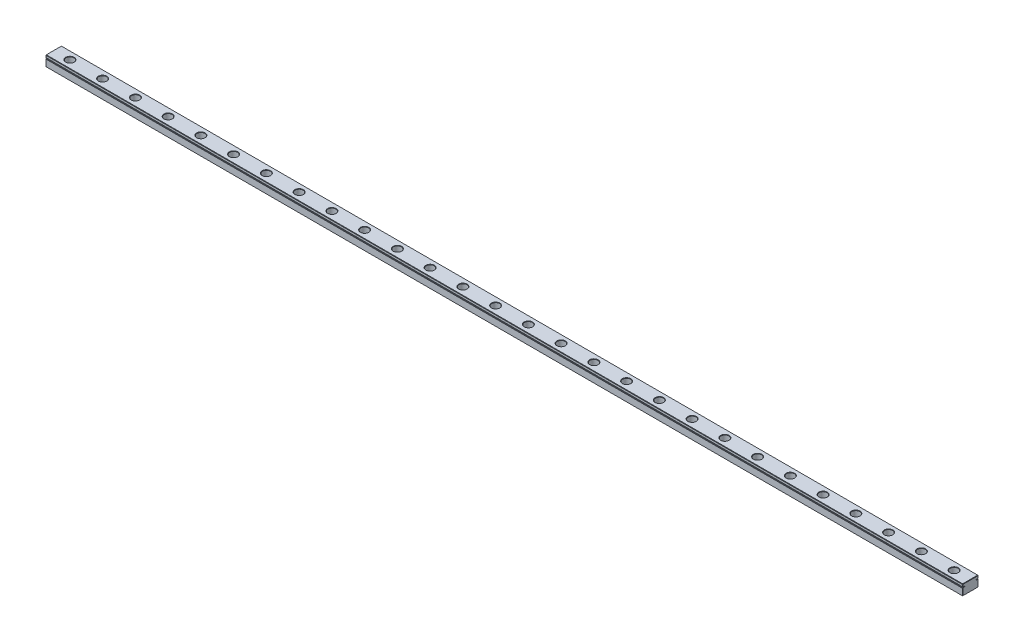
SolidWorks part; units mm, degrees
note: The reader was unsure of these and kept them because the rebuilt part matched: shared geometry of "Sketch5<3>".
ref_plane "Front Plane" through (0, 0, 0) normal (0, 0, 1) x (1, 0, 0)
ref_plane "Top Plane" through (0, 0, 0) normal (0, 1, 0) x (1, 0, 0)
ref_plane "Right Plane" through (0, 0, 0) normal (1, 0, 0) x (0, 0, -1)
sketch "Sketch1" plane through (0, 0, 0) normal (1, 0, 0) x (0, 0, -1)
  line L1 (6, -4) -> (-6, -4)
  line L2 (6, -4) -> (6, 4)
  line L3 (6, 4) -> (-6, 4)
  line L4 (-6, -4) -> (-6, 4)
  line L5 (6, -4) -> (-6, 4) construction
  line L6 (6, 4) -> (-6, -4) construction
  point P0 (0, 0)
  dimension "D1" = 8
  dimension "D2" = 12
extrude "Boss-Extrude1" add sketch "Sketch1" along normal blind 700
sketch "Sketch4" plane through (0, 0, 0) normal (-1, 0, 0) x (0, 0, 1)
  line L0 (-6, 2) -> (-4.25, 2)
  line L1 (-6, -4) -> (-6, 4) construction
  line L2 (-4.25, 2) -> (-4.25, 1.5)
  line L3 (-4.25, 1.5) -> (-6, 1.5)
  line L4 (-6, 1.5) -> (-6, 2)
  line L5 (0, 0) -> (0, -1.3388) construction
  line L6 (6, 1.5) -> (6, 2)
  line L7 (4.25, 1.5) -> (6, 1.5)
  line L8 (4.25, 2) -> (4.25, 1.5)
  line L9 (6, 2) -> (4.25, 2)
  line L10 (-6, 4) -> (6, 4) construction
  dimension "D1" = 2
  dimension "D2" = 0.5
  dimension "D3" = 1.75
extrude "Cut-Extrude3" cut sketch "Sketch4" against normal up to next
sketch "Sketch5" plane through (0, 4, 0) normal (0, 1, 0) x (1, 0, 0)
  line L0 (350, 6) -> (350, -6) construction
  line L1 (700, 6) -> (0, 6) construction
  line L2 (700, -6) -> (0, -6) construction
  line L3 (350, 0) -> (337.5, 0) construction
  circle A0 centre (337.5, 0) radius 1.75
  circle A1 centre (337.5, 0) radius 3
  dimension "D2" = 3.5
  dimension "D3" = 6
  dimension "D1" = 25
extrude "Cut-Extrude4" cut sketch "Sketch5" against normal through all contours A0
extrude "Cut-Extrude5" cut sketch "Sketch5<3>" against normal blind 4.5
sketch "Sketch5<3>" plane through (0, 4, 0) normal (0, 1, 0) x (1, 0, 0) same geometry as "Sketch5"
pattern_linear "LPattern1" count 14 spacing 25 along (-1, 0, 0) count 15 spacing 25 along (1, 0, 0) of "Cut-Extrude4", "Cut-Extrude5"
chamfer "Chamfer1" distance 0.25 angle 45 82 edges at (337.5, -4, 1.75) (362.5, -4, 1.75) (387.5, -4, 1.75) (412.5, -4, 1.75) (437.5, -4, 1.75) (462.5, -4, 1.75) (487.5, -4, 1.75) (512.5, -4, 1.75) (537.5, -4, 1.75) (562.5, -4, 1.75) (587.5, -4, 1.75) (612.5, -4, 1.75) (637.5, -4, 1.75) (662.5, -4, 1.75) (687.5, -4, 1.75) (312.5, -4, 1.75) (287.5, -4, 1.75) (262.5, -4, 1.75) (237.5, -4, 1.75) (212.5, -4, 1.75) (187.5, -4, 1.75) (162.5, -4, 1.75) (137.5, -4, 1.75) (112.5, -4, 1.75) (87.5, -4, 1.75) (62.5, -4, 1.75) (37.5, -4, 1.75) (12.5, -4, 1.75) (700, -4, 0) (350, 2, -6) (700, 3, -6) (350, -4, -6) (700, -1.25, -6) (350, 1.5, -6) (700, 3, 6) (350, 2, 6) (350, -4, 6) (700, -1.25, 6) (350, 1.5, 6) (0, -4, 0) (0, -1.25, -6) (0, 1.5, -5.125) (0, 1.75, -4.25) (0, 2, -5.125) (0, 3, -6) (0, -1.25, 6) (0, 1.5, 5.125) (0, 1.75, 4.25) (0, 2, 5.125) (0, 3, 6) (350, 4, -6) (700, 4, 0) (350, 4, 6) (0, 4, 0) (337.5, 4, 3) (362.5, 4, 3) (387.5, 4, 3) (412.5, 4, 3) (437.5, 4, 3) (462.5, 4, 3) (487.5, 4, 3) (512.5, 4, 3) (537.5, 4, 3) (562.5, 4, 3) (587.5, 4, 3) (612.5, 4, 3) (637.5, 4, 3) (662.5, 4, 3) (687.5, 4, 3) (312.5, 4, 3) (287.5, 4, 3) (262.5, 4, 3) (237.5, 4, 3) (212.5, 4, 3) (187.5, 4, 3) (162.5, 4, 3) (137.5, 4, 3) (112.5, 4, 3) (87.5, 4, 3) (62.5, 4, 3) (37.5, 4, 3) (12.5, 4, 3)
equation "\"RailLength\"= 700"
equation "\"D1@Boss-Extrude1\"=\"RailLength\""
equation "\"D1@LPattern1\"=int( \"RailLength\"/25/2)"
equation "\"D2@LPattern1\"=int( \"RailLength\"/25/2)+1"
